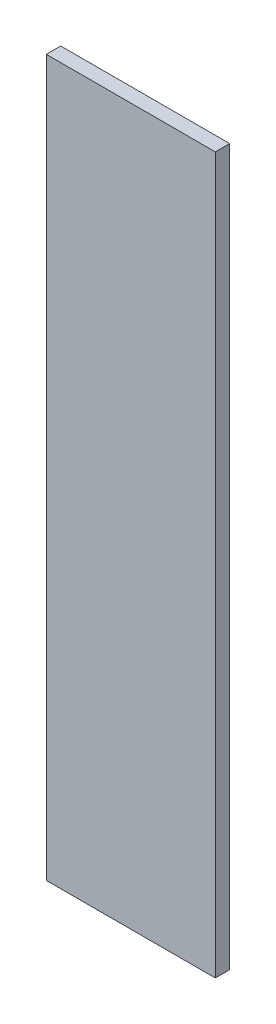
SolidWorks part; units mm, degrees
ref_plane "Front Plane" through (0, 0, 0) normal (0, 0, 1) x (1, 0, 0)
ref_plane "Top Plane" through (0, 0, 0) normal (0, 1, 0) x (1, 0, 0)
ref_plane "Right Plane" through (0, 0, 0) normal (1, 0, 0) x (0, 0, -1)
sketch "Sketch1" plane through (0, 0, 0) normal (0, 0, 1) x (1, 0, 0)
  line L1 (-57, 36) -> (-33.5, 36)
  line L2 (-57, 36) -> (-57, -63.5)
  line L3 (-57, -63.5) -> (-33.5, -63.5)
  line L4 (-33.5, 36) -> (-33.5, -63.5)
  dimension "D1" = 99.5
  dimension "D2" = 23.5
extrude "Boss-Extrude1" add sketch "Sketch1" along normal blind 2
